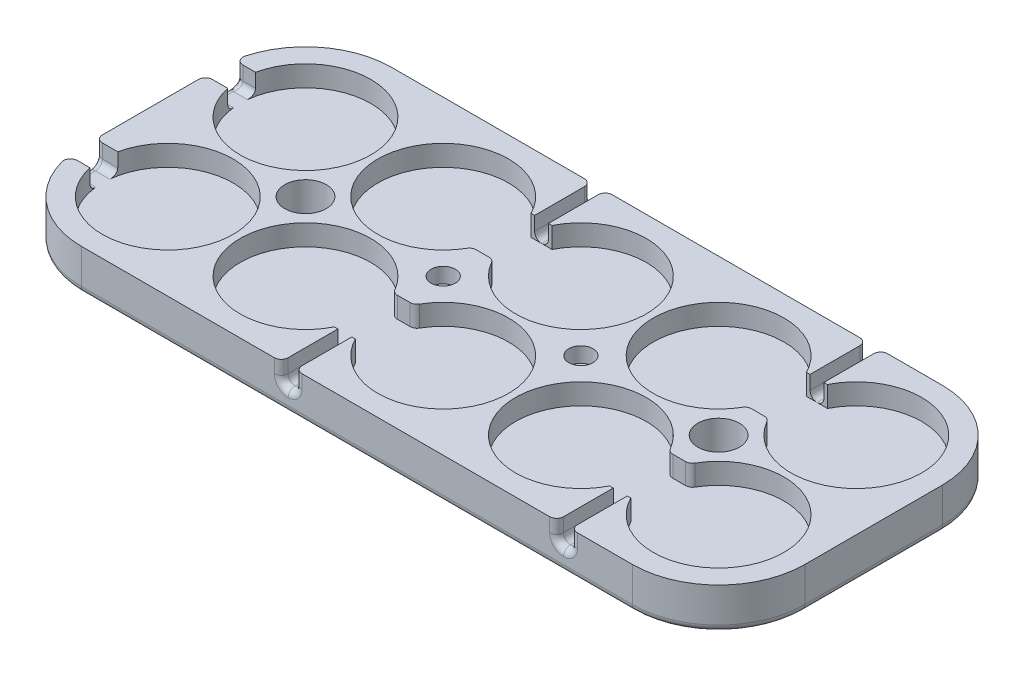
SolidWorks part; units mm, degrees
ref_plane "Front Plane" through (0, 0, 0) normal (0, 0, 1) x (1, 0, 0)
ref_plane "Top Plane" through (0, 0, 0) normal (0, 1, 0) x (1, 0, 0)
ref_plane "Right Plane" through (0, 0, 0) normal (1, 0, 0) x (0, 0, -1)
sketch "Sketch2" plane through (0, 0, 0) normal (0, 1, 0) x (1, 0, 0)
  line L0 (-39.7, 9.925) -> (-19.85, 9.925) construction
  line L1 (-19.85, 9.925) -> (0, 9.925) construction
  line L2 (0, 9.925) -> (19.85, 9.925) construction
  line L3 (19.85, 9.925) -> (39.7, 9.925) construction
  line L4 (39.7, 9.925) -> (39.7, -9.925) construction
  line L5 (39.7, -9.925) -> (19.85, -9.925) construction
  line L6 (19.85, -9.925) -> (0, -9.925) construction
  line L7 (0, -9.925) -> (-19.85, -9.925) construction
  line L8 (-39.7, 9.925) -> (-39.7, -9.925) construction
  line L9 (-39.7, -9.925) -> (-19.85, -9.925) construction
  line L10 (-39.7, 9.925) -> (39.7, -9.925) construction
  line L11 (-30.275, 9.925) -> (-29.275, 9.925) construction
  line L16 (-39.7, 0.5) -> (-39.7, -0.5) construction
  line L17 (-39.7, 22.35) -> (39.7, 22.35)
  line L19 (52.125, -9.925) -> (52.125, 9.925)
  line L20 (39.7, -22.35) -> (-39.7, -22.35)
  line L21 (-52.125, -9.925) -> (-52.125, 9.925)
  line L22 (-39.7, -9.925) -> (-52.125, -9.925) construction
  circle A0 centre (-39.7, 9.925) radius 9.425
  circle A1 centre (-19.85, 9.925) radius 9.425
  circle A2 centre (-39.7, -9.925) radius 9.425
  circle A3 centre (-19.85, -9.925) radius 9.425
  circle A4 centre (0, 9.925) radius 9.425
  circle A5 centre (0, -9.925) radius 9.425
  circle A6 centre (19.85, 9.925) radius 9.425
  circle A7 centre (19.85, -9.925) radius 9.425
  circle A8 centre (39.7, 9.925) radius 9.425
  circle A9 centre (39.7, -9.925) radius 9.425
  circle A10 centre (-39.7, 9.925) radius 12.425
  circle A11 centre (-39.7, -9.925) radius 12.425
  circle A12 centre (39.7, -9.925) radius 12.425
  circle A13 centre (39.7, 9.925) radius 12.425
  dimension "D1" = 18.85
  dimension "D2" = 1
  dimension "D3" = 1
  dimension "D4" = 3
extrude "Boss-Extrude1" add sketch "Sketch2" along normal blind 3 contours A13 L17 A10 A1 A11 A3 L20 A12 A7 A6 A5 A4 | A12 A13 A6 A8 | A13 A9 A12 A7 | A13 A12 L19 | A9 A13 A12 A8 | A11 A10 L21 | A11 A10 A1 A0 | A3 A11 A10 A2 | A10 A11 A0 A2 region at (-32.8744, 0, -19.9125) region at (0, 0, 0) region at (48.2539, 0, -18.4789) region at (-50.7094, 0, 0) region at (50.7094, 0, 0) region at (-50.5254, 0, 4.5259) region at (-39.7, 0, 0) region at (48.2539, 0, 18.4789) region at (39.7, 0, 0)
sketch "Sketch3" plane through (0, 0, 0) normal (0, 1, 0) x (1, 0, 0)
  line L0 (52.125, -9.925) -> (52.125, 9.925) construction
  line L1 (-52.125, -22.35) -> (52.125, -22.35)
  line L2 (-52.125, -22.35) -> (-52.125, 22.35)
  line L3 (-52.125, 22.35) -> (52.125, 22.35)
  line L4 (52.125, -22.35) -> (52.125, 22.35)
  line L5 (-52.125, -9.925) -> (-52.125, 9.925) construction
  line L6 (39.7, -22.35) -> (-39.7, -22.35) construction
  line L7 (-39.7, 22.35) -> (39.7, 22.35) construction
  circle A0 centre (-39.7, -9.925) radius 12.425
  circle A1 centre (-39.7, 9.925) radius 12.425
  circle A2 centre (39.7, 9.925) radius 12.425
  circle A3 centre (39.7, -9.925) radius 12.425
  circle A4 centre (-39.7, 9.925) radius 9.425 construction
  arc A5 (-39.7, 22.35) -> (-52.125, 9.925) centre (-39.7, 9.925) ccw construction
  arc A6 (-52.125, -9.925) -> (-39.7, -22.35) centre (-39.7, -9.925) ccw construction
  arc A7 (39.7, -22.35) -> (52.125, -9.925) centre (39.7, -9.925) ccw construction
  arc A8 (52.125, 9.925) -> (39.7, 22.35) centre (39.7, 9.925) ccw construction
extrude "Boss-Extrude2" add sketch "Sketch3" against normal blind 3 contours A3 A2 L3 A1 A0 L1 | A1 A0 | A0 A1 | A0 A1 | A1 L2 A0 | A3 A2 | A2 A3 | A3 A2 | A3 L4 A2 region at (0, 0, 0) region at (-39.7, 0, 11.0895) region at (-50.7094, 0, 0) region at (39.7, 0, 11.0895) region at (-39.7, 0, -11.0895) region at (-39.7, 0, 0) region at (39.7, 0, 0) region at (39.7, 0, -11.0895) region at (50.7094, 0, 0)
sketch "Sketch4" plane through (0, 0, 0) normal (0, 1, 0) x (1, 0, 0)
  line L1 (39.7, -5.675) -> (19.85, -5.675)
  line L2 (39.7, -5.675) -> (39.7, -14.175)
  line L3 (39.7, -14.175) -> (19.85, -14.175)
  line L4 (19.85, -5.675) -> (19.85, -14.175)
  line L5 (0, -5.675) -> (-19.85, -5.675)
  line L6 (0, -5.675) -> (0, -14.175)
  line L7 (0, -14.175) -> (-19.85, -14.175)
  line L8 (-19.85, -5.675) -> (-19.85, -14.175)
  line L13 (-19.85, 14.175) -> (0, 14.175)
  line L14 (-19.85, 14.175) -> (-19.85, 5.675)
  line L15 (-19.85, 5.675) -> (0, 5.675)
  line L16 (0, 14.175) -> (0, 5.675)
  line L17 (19.85, 14.175) -> (39.7, 14.175)
  line L18 (19.85, 14.175) -> (19.85, 5.675)
  line L19 (19.85, 5.675) -> (39.7, 5.675)
  line L20 (39.7, 14.175) -> (39.7, 5.675)
  circle A2 centre (-19.85, -9.925) radius 9.425 construction
  circle A3 centre (0, -9.925) radius 9.425 construction
  circle A4 centre (19.85, -9.925) radius 9.425 construction
  circle A5 centre (39.7, -9.925) radius 9.425 construction
  circle A6 centre (39.7, 9.925) radius 9.425 construction
  circle A7 centre (19.85, 9.925) radius 9.425 construction
  circle A8 centre (-19.85, 9.925) radius 9.425 construction
  circle A9 centre (0, 9.925) radius 9.425 construction
  point P26 (-19.85, -9.925)
  point P29 (0, -9.925)
  point P34 (19.85, -9.925)
  point P35 (39.7, -9.925)
  point P40 (39.7, 9.925)
  point P41 (19.85, 9.925)
  point P46 (-19.85, 9.925)
  point P47 (0, 9.925)
  dimension "D1" = 8.5
extrude "Cut-Extrude1" cut sketch "Sketch4" along normal through all
sketch "Sketch5" plane through (0, 0, 0) normal (0, 1, 0) x (1, 0, 0)
  line L0 (-52.125, -9.925) -> (-52.125, 9.925) construction
  line L1 (-10.925, 10.675) -> (-8.925, 10.675)
  line L2 (-10.925, 10.675) -> (-10.925, 22.35)
  line L3 (-10.925, 22.35) -> (-8.925, 22.35)
  line L4 (-8.925, 10.675) -> (-8.925, 22.35)
  line L5 (28.775, 10.675) -> (30.775, 10.675)
  line L6 (28.775, 10.675) -> (28.775, 22.35)
  line L7 (28.775, 22.35) -> (30.775, 22.35)
  line L8 (30.775, 10.675) -> (30.775, 22.35)
  line L9 (28.775, -10.675) -> (30.775, -10.675)
  line L10 (28.775, -10.675) -> (28.775, -22.35)
  line L11 (28.775, -22.35) -> (30.775, -22.35)
  line L12 (30.775, -10.675) -> (30.775, -22.35)
  line L13 (-10.925, -10.675) -> (-8.925, -10.675)
  line L14 (-10.925, -10.675) -> (-10.925, -22.35)
  line L15 (-10.925, -22.35) -> (-8.925, -22.35)
  line L16 (-8.925, -10.675) -> (-8.925, -22.35)
  line L17 (-44.7, -11.925) -> (-52.125, -11.925)
  line L18 (-44.7, -11.925) -> (-44.7, -7.925)
  line L19 (-44.7, -7.925) -> (-52.125, -7.925)
  line L20 (-52.125, -11.925) -> (-52.125, -7.925)
  line L21 (-39.7, 22.35) -> (39.7, 22.35) construction
  line L22 (39.7, -22.35) -> (-39.7, -22.35) construction
  line L23 (-39.7, -9.925) -> (-44.7, -9.925) construction
  line L24 (-44.7, 7.925) -> (-52.125, 7.925)
  line L25 (-44.7, 7.925) -> (-44.7, 11.925)
  line L26 (-44.7, 11.925) -> (-52.125, 11.925)
  line L27 (-52.125, 7.925) -> (-52.125, 11.925)
  line L28 (-39.7, 9.925) -> (-44.7, 9.925) construction
  line L29 (-9.925, 10.675) -> (-9.925, 5.675) construction
  line L30 (-11.4376, 5.675) -> (-8.4124, 5.675) construction
  line L31 (29.775, 5.675) -> (29.775, 10.675) construction
  line L32 (28.2624, 5.675) -> (31.2876, 5.675) construction
  line L33 (-9.925, -10.675) -> (-9.925, -5.675) construction
  line L34 (-8.4124, -5.675) -> (-11.4376, -5.675) construction
  line L35 (29.775, -5.675) -> (29.775, -10.675) construction
  line L36 (31.2876, -5.675) -> (28.2624, -5.675) construction
  dimension "D1" = 4
  dimension "D2" = 5
  dimension "D3" = 5
  dimension "D4" = 2
extrude "Cut-Extrude2" cut sketch "Sketch5" along normal through all
sketch "Sketch7" plane through (0, 0, 0) normal (0, 1, 0) x (1, 0, 0)
  line L0 (-29.775, 0) -> (-9.925, 0) construction
  line L1 (-9.925, 0) -> (9.925, 0) construction
  line L2 (9.925, 0) -> (29.775, 0) construction
  circle A1 centre (-29.775, 0) radius 3
  circle A2 centre (-9.925, 0) radius 1.75
  circle A3 centre (9.925, 0) radius 1.75
  circle A4 centre (29.775, 0) radius 3
  circle A5 centre (-29.775, 0) radius 4.6111 construction
  arc A6 (-11.4376, -5.675) -> (-11.4376, -14.175) centre (-19.85, -9.925) ccw construction
  circle A7 centre (-39.7, 9.925) radius 9.425 construction
  dimension "D1" = 6
  dimension "D2" = 3.5
extrude "Cut-Extrude3" cut sketch "Sketch7" along normal through all both and the other way through all
sketch "Sketch8" plane through (0, -3, 0) normal (0, -1, 0) x (1, 0, 0)
  circle A0 centre (9.925, 0) radius 3
  circle A1 centre (-9.925, 0) radius 3
  circle A2 centre (-9.925, 0) radius 1.75 construction
  circle A3 centre (9.925, 0) radius 1.75 construction
  circle A4 centre (29.775, 0) radius 3 construction
extrude "Cut-Extrude4" cut sketch "Sketch8" against normal blind 3.5
fillet "Fillet1" radius 1 40 edges at (28.775, 1.5, 22.35) (30.775, 1.5, 22.35) (-10.925, 1.5, 22.35) (-8.925, 1.5, 22.35) (-52.125, 1.5, 7.925) (-8.925, 1.5, -22.35) (-10.925, 1.5, -22.35) (30.775, 1.5, -22.35) (28.775, 1.5, -22.35) (29.775, 0, 22.35) (28.775, 0, 18.2625) (30.775, 0, 18.2625) (-9.925, 0, 22.35) (-8.925, 0, 18.2625) (-10.925, 0, 18.2625) (-50.4367, 0, 11.925) (-50.5177, 0, 7.925) (-52.125, 0, 8.925) (-9.925, 0, -22.35) (-10.925, 0, -18.2625) (-8.925, 0, -18.2625) (29.775, 0, -22.35) (28.775, 0, -18.2625) (30.775, 0, -18.2625) (28.2624, 1.5, 5.675) (31.2876, 1.5, 5.675) (-8.4124, 1.5, 5.675) (-11.4376, 1.5, 5.675) (-11.4376, 1.5, -5.675) (-8.4124, 1.5, -5.675) (28.2624, 1.5, -5.675) (31.2876, 1.5, -5.675) (-51.963, 1.5, 11.925) (-52.0844, 0, 10.9283) (-52.125, 1.5, -7.925) (-51.963, 1.5, -11.925) (-52.125, 0, -8.925) (-52.0844, 0, -10.9283) (-50.5177, 0, -7.925) (-50.4367, 0, -11.925)
fillet "Fillet2" radius 1 8 edges at (-48.4858, -3, 18.7108) (-52.125, -3, 0) (-48.4858, -3, -18.7108) (0, -3, -22.35) (48.4858, -3, -18.7108) (52.125, -3, 0) (48.4858, -3, 18.7108) (0, -3, 22.35)
sketch "Sketch9" plane through (0, -3, 0) normal (0, -1, 0) x (1, 0, 0)
  line L0 (-48.5919, 6.8) -> (-30.8081, 6.8) construction
  line L2 (-28.7419, 13.05) -> (8.8919, 13.05) construction
  line L4 (10.9581, 13.05) -> (48.5919, 13.05) construction
  line L5 (-48.5919, -13.05) -> (-30.8081, -13.05) construction
  line L6 (-28.7419, -13.05) -> (8.8919, -13.05) construction
  line L8 (10.9581, -13.05) -> (48.5919, -13.05) construction
  line L10 (-48.5919, 13.05) -> (-30.8081, 13.05) construction
  line L11 (-39.7, 13.05) -> (-39.7, 6.8) construction
  line L12 (-48.5919, -6.8) -> (-30.8081, -6.8) construction
  line L13 (-39.7, -6.8) -> (-39.7, -13.05) construction
  circle A0 centre (39.7, 9.925) radius 9.425 construction
  circle A1 centre (19.85, 9.925) radius 9.425 construction
  circle A2 centre (0, 9.925) radius 9.425 construction
  circle A3 centre (-19.85, 9.925) radius 9.425 construction
  circle A4 centre (-39.7, 9.925) radius 9.425 construction
  circle A5 centre (-39.7, -9.925) radius 9.425 construction
  circle A6 centre (-19.85, -9.925) radius 9.425 construction
  circle A7 centre (0, -9.925) radius 9.425 construction
  circle A8 centre (19.85, -9.925) radius 9.425 construction
  circle A9 centre (39.7, -9.925) radius 9.425 construction
  arc A10 (-48.9104, 7.925) -> (-48.9104, 11.925) centre (-39.7, 9.925) ccw construction
  text T0 "<b>B+</b>" font "Arial Rounded MT Bold" height 6.5
  text T1 "<b>B-</b>" font "Arial Rounded MT Bold" height 6.5
  text T2 "<b>2+</b>" font "Arial Rounded MT Bold" height 6.5
  text T4 "<b>4+</b>" font "Arial Rounded MT Bold" height 6.5
  text T7 "<b>8+</b>" font "Arial Rounded MT Bold" height 6.5
  text T9 "<b>6+</b>" font "Arial Rounded MT Bold" height 6.5
  dimension "D1" = 6.25
  dimension "D2" = 6.25
extrude "Cut-Extrude5" cut sketch "Sketch9" against normal blind 0.5
sketch "Sketch10" plane through (0, 0.5, 0) normal (0, -1, 0) x (1, 0, 0)
  circle A0 centre (-9.925, 0) radius 3
  circle A1 centre (9.925, 0) radius 3
extrude "Boss-Extrude3" add sketch "Sketch10" against normal blind 0.3
